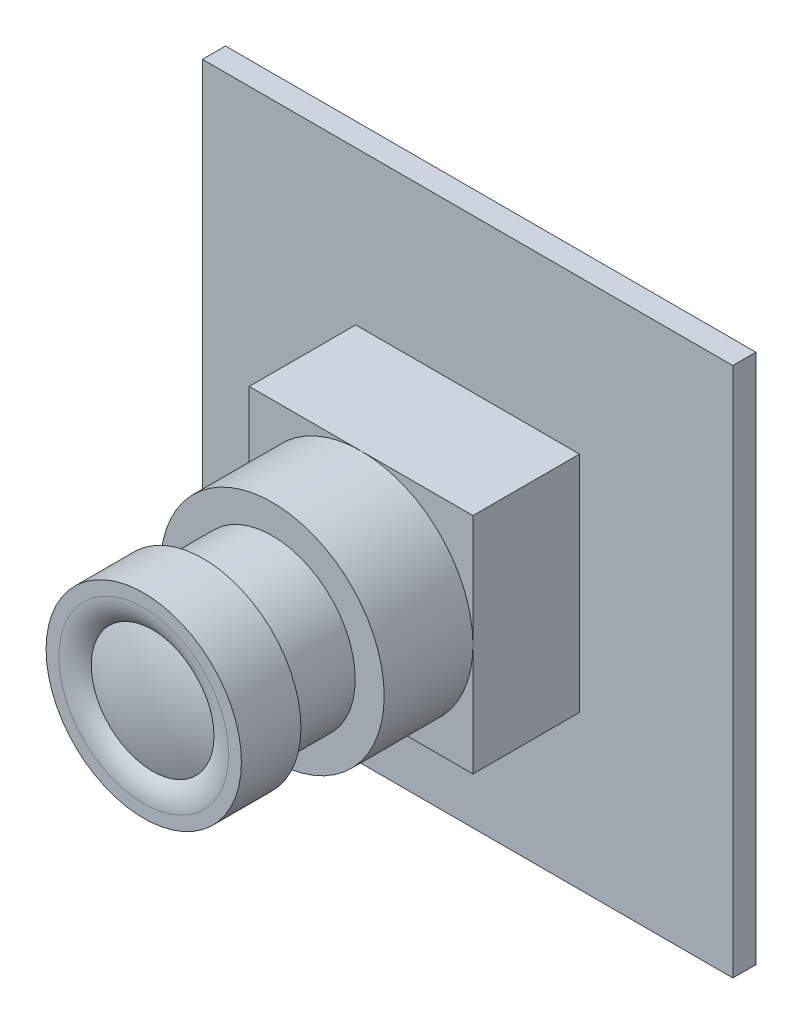
SolidWorks part; units mm, degrees
ref_plane "Front Plane" through (0, 0, 0) normal (0, 0, 1) x (1, 0, 0)
ref_plane "Top Plane" through (0, 0, 0) normal (0, 1, 0) x (1, 0, 0)
ref_plane "Right Plane" through (0, 0, 0) normal (1, 0, 0) x (0, 0, -1)
sketch "Sketch1" plane through (0, 0, 0) normal (0, 0, 1) x (1, 0, 0)
  line L1 (0, 37.9349) -> (37.9349, 37.9349)
  line L2 (0, 37.9349) -> (0, 0)
  line L3 (0, 0) -> (37.9349, 0)
  line L4 (37.9349, 37.9349) -> (37.9349, 0)
  dimension "D1" = 37.9349
extrude "Boss-Extrude1" add sketch "Sketch1" along normal blind 1.651
sketch "Sketch2" plane through (0, 0, 1.651) normal (0, 0, 1) x (1, 0, 0)
  line L0 (37.9349, 18.9675) -> (26.9685, 18.9675) construction
  line L1 (10.9665, 26.9685) -> (26.9684, 26.9685)
  line L2 (10.9665, 26.9685) -> (10.9665, 10.9665)
  line L3 (10.9665, 10.9665) -> (26.9685, 10.9665)
  line L4 (26.9684, 26.9685) -> (26.9685, 10.9665)
  line L5 (0, 0) -> (37.9349, 0) construction
  line L6 (37.9349, 0) -> (37.9349, 37.9349) construction
  line L7 (18.9674, 37.9349) -> (18.9675, 26.9685) construction
  line L10 (37.9349, 37.9349) -> (0, 37.9349) construction
  dimension "D1" = 16.002
extrude "Boss-Extrude2" add sketch "Sketch2" along normal blind 7.62
sketch "Sketch3" plane through (0, 0, 9.271) normal (0, 0, 1) x (1, 0, 0)
  line L1 (26.9684, 26.9685) -> (10.9665, 26.9685) construction
  line L2 (26.9685, 10.9665) -> (26.9684, 26.9685) construction
  line L3 (10.9665, 26.9685) -> (10.9665, 10.9665) construction
  line L4 (10.9665, 10.9665) -> (26.9685, 10.9665) construction
  circle A0 centre (18.9675, 18.9675) radius 8.001
extrude "Boss-Extrude3" add sketch "Sketch3" along normal blind 6.35
sketch "Sketch4" plane through (0, 0, 15.621) normal (0, 0, 1) x (1, 0, 0)
  circle A0 centre (18.9675, 18.9675) radius 5.9309
  circle A1 centre (18.9675, 18.9675) radius 8.001 construction
  dimension "D1" = 11.8618
extrude "Boss-Extrude4" add sketch "Sketch4" along normal blind 4.9403
sketch "Sketch5" plane through (0, 0, 20.5613) normal (0, 0, 1) x (1, 0, 0)
  circle A0 centre (18.9675, 18.9675) radius 6.985
  circle A1 centre (18.9675, 18.9675) radius 5.9309 construction
  dimension "D1" = 13.97
extrude "Boss-Extrude5" add sketch "Sketch5" along normal blind 4.2545
sketch "Sketch6" plane through (0, 0, 24.8158) normal (0, 0, 1) x (1, 0, 0)
  circle A0 centre (18.9675, 18.9675) radius 4.3878
  circle A1 centre (18.9675, 18.9675) radius 6.985 construction
  dimension "D1" = 8.7757
extrude "Cut-Extrude1" cut sketch "Sketch6" against normal blind 0.635
fillet "Fillet2" radius 2.54 1 edges at (23.3553, 18.9675, 24.8158)
dome "Dome1" faces to dome 1 distance 0.762 reverse direction no elliptical dome no face at (23.3553, 18.9675, 24.1808) parameters "D1"=0.762
sketch "Sketch9" plane through (0, 0, 1.651) normal (0, 0, 1) x (1, 0, 0)
  line L0 (32.8168, 32.8168) -> (37.9349, 32.8168) construction
  line L1 (0, 0) -> (37.9349, 0) construction
  line L2 (37.9349, 0) -> (37.9349, 37.9349) construction
  line L3 (32.8168, 37.9349) -> (32.8168, 32.8168) construction
  line L4 (0, 37.9349) -> (0, 0) construction
  line L5 (37.9349, 37.9349) -> (0, 37.9349) construction
  line L6 (5.1181, 37.9349) -> (5.1181, 32.8168) construction
  line L7 (0, 32.8168) -> (5.1181, 32.8168) construction
  line L8 (5.1181, 0) -> (5.1181, 5.1181) construction
  line L9 (0, 5.1181) -> (5.1181, 5.1181) construction
  line L10 (37.9349, 5.1181) -> (32.8168, 5.1181) construction
  line L11 (32.8168, 0) -> (32.8168, 5.1181) construction
  circle A0 centre (32.8168, 32.8168) radius 1.1176
  circle A1 centre (5.1181, 32.8168) radius 1.1176
  circle A2 centre (5.1181, 5.1181) radius 1.1176
  circle A3 centre (32.8168, 5.1181) radius 1.1176
  dimension "D1" = 2.2352
  dimension "D2" = 5.1181
